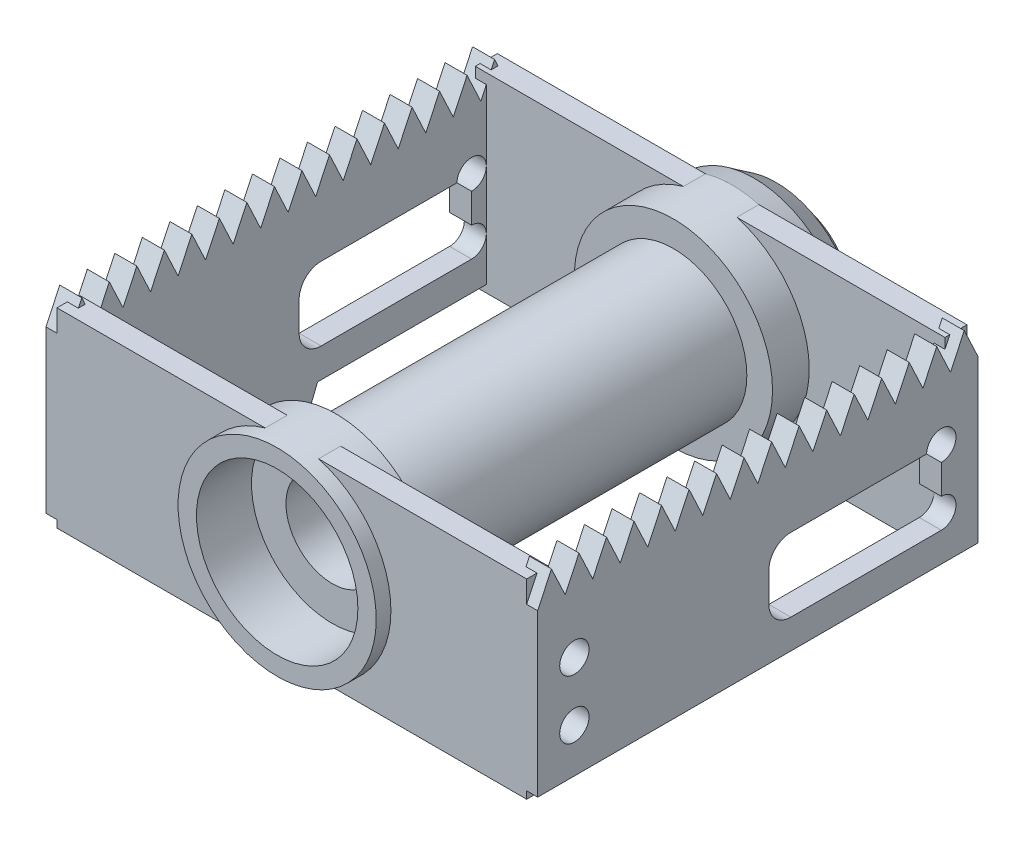
SolidWorks part; units mm, degrees
material "6061-T6 (SS)"
ref_plane "Alzado" through (0, 0, 0) normal (0, 0, 1) x (1, 0, 0)
ref_plane "Planta" through (0, 0, 0) normal (0, 1, 0) x (1, 0, 0)
ref_plane "Vista lateral" through (0, 0, 0) normal (1, 0, 0) x (0, 0, -1)
sketch "Sk_Eje_cuerpo" plane through (0, 0, 0) normal (0, 1, 0) x (1, 0, 0)
  line L0 (-183.5, 84) -> (-186, 84)
  line L1 (-186, 84) -> (-186, 92)
  line L2 (-186, 92) -> (-182.5, 92)
  line L3 (-182.5, 92) -> (-182.5, 138)
  line L4 (-182.5, 138) -> (-186, 138)
  line L5 (-186, 138) -> (-186, 146)
  line L6 (-186, 146) -> (-185.3, 149)
  line L7 (-185.3, 149) -> (-183.3, 152)
  line L8 (-183.3, 152) -> (-180, 154.5)
  line L9 (-180, 154.5) -> (-176.5, 155.7)
  line L10 (-176.5, 155.7) -> (-172.5, 156)
  line L11 (-172.5, 156) -> (-172.5, 147)
  line L12 (-172.5, 147) -> (-183.5, 147)
  line L13 (-183.5, 147) -> (-183.5, 138.5)
  line L14 (-183.5, 138.5) -> (-178.8, 138.5)
  line L15 (-178.8, 138.5) -> (-178.8, 91.5)
  line L16 (-178.8, 91.5) -> (-183.5, 91.5)
  line L17 (-183.5, 91.5) -> (-183.5, 84)
  line L18 (-172.5, 62.1) -> (-172.5, 160) construction
revolve "Eje_cuerpo" add sketch "Sk_Eje_cuerpo" angle 360 about L18
sketch "Sk_Placa_delantera" plane through (0, 0, 0) normal (1, 0, 0) x (0, 0, -1)
  line L0 (86, -12) -> (112, -12)
  line L1 (112, -12) -> (116, -22)
  line L2 (116, -22) -> (120, -12)
  line L3 (120, -12) -> (146, -12)
  line L4 (146, -12) -> (146, 10)
  line L5 (146, 10) -> (144.125, 14)
  line L6 (144.125, 14) -> (142.25, 10)
  line L7 (142.25, 10) -> (140.375, 14)
  line L8 (140.375, 14) -> (138.5, 10)
  line L9 (138.5, 10) -> (136.625, 14)
  line L10 (136.625, 14) -> (134.75, 10)
  line L11 (134.75, 10) -> (132.875, 14)
  line L12 (132.875, 14) -> (131, 10)
  line L13 (131, 10) -> (129.125, 14)
  line L14 (129.125, 14) -> (127.25, 10)
  line L15 (127.25, 10) -> (125.375, 14)
  line L16 (125.375, 14) -> (123.5, 10)
  line L17 (123.5, 10) -> (121.625, 14)
  line L18 (121.625, 14) -> (119.75, 10)
  line L19 (119.75, 10) -> (117.875, 14)
  line L20 (117.875, 14) -> (116, 10)
  line L21 (116, 10) -> (114.125, 14)
  line L22 (114.125, 14) -> (112.25, 10)
  line L23 (112.25, 10) -> (110.375, 14)
  line L24 (110.375, 14) -> (108.5, 10)
  line L25 (108.5, 10) -> (106.625, 14)
  line L26 (106.625, 14) -> (104.75, 10)
  line L27 (104.75, 10) -> (102.875, 14)
  line L28 (102.875, 14) -> (101, 10)
  line L29 (101, 10) -> (99.125, 14)
  line L30 (99.125, 14) -> (97.25, 10)
  line L31 (97.25, 10) -> (95.375, 14)
  line L32 (95.375, 14) -> (93.5, 10)
  line L33 (93.5, 10) -> (91.625, 14)
  line L34 (91.625, 14) -> (89.75, 10)
  line L35 (89.75, 10) -> (87.875, 14)
  line L36 (87.875, 14) -> (86, 10)
  line L37 (86, 10) -> (86, -12)
extrude "Placa_delantera" add sketch "Sk_Placa_delantera" along normal blind 3 from offset 206 offset against normal yes
sketch3d "Sk_Agujero_Placa_delantera_1"
  line L0 (-201.5, -6, -91) -> (-207.5, -6, -91)
  dimension "D1" = 6
sweep "Agujero_Placa_delantera_1" cut path "Sk_Agujero_Placa_delantera_1" circular profile diameter 4 parameters "D3"=4
sketch3d "Sk_Agujero_Placa_delantera_2"
  line L0 (-201.5, 2, -91) -> (-207.5, 2, -91)
  dimension "D1" = 6
sweep "Agujero_Placa_delantera_2" cut path "Sk_Agujero_Placa_delantera_2" circular profile diameter 4 parameters "D3"=4
sketch3d "Sk_Agujero_Placa_delantera_3"
  line L0 (-201.5, -6, -141) -> (-207.5, -6, -141)
  dimension "D1" = 6
sweep "Agujero_Placa_delantera_3" cut path "Sk_Agujero_Placa_delantera_3" circular profile diameter 4 parameters "D3"=4
sketch3d "Sk_Agujero_Placa_delantera_4"
  line L0 (-201.5, 2, -141) -> (-207.5, 2, -141)
  dimension "D1" = 6
sweep "Agujero_Placa_delantera_4" cut path "Sk_Agujero_Placa_delantera_4" circular profile diameter 4 parameters "D3"=4
sketch "Sk_Placa_trasera" plane through (0, 0, 0) normal (1, 0, 0) x (0, 0, -1)
  line L0 (86, -12) -> (146, -12)
  line L1 (146, -12) -> (146, 10)
  line L2 (146, 10) -> (144.125, 14)
  line L3 (144.125, 14) -> (142.25, 10)
  line L4 (142.25, 10) -> (140.375, 14)
  line L5 (140.375, 14) -> (138.5, 10)
  line L6 (138.5, 10) -> (136.625, 14)
  line L7 (136.625, 14) -> (134.75, 10)
  line L8 (134.75, 10) -> (132.875, 14)
  line L9 (132.875, 14) -> (131, 10)
  line L10 (131, 10) -> (129.125, 14)
  line L11 (129.125, 14) -> (127.25, 10)
  line L12 (127.25, 10) -> (125.375, 14)
  line L13 (125.375, 14) -> (123.5, 10)
  line L14 (123.5, 10) -> (121.625, 14)
  line L15 (121.625, 14) -> (119.75, 10)
  line L16 (119.75, 10) -> (117.875, 14)
  line L17 (117.875, 14) -> (116, 10)
  line L18 (116, 10) -> (114.125, 14)
  line L19 (114.125, 14) -> (112.25, 10)
  line L20 (112.25, 10) -> (110.375, 14)
  line L21 (110.375, 14) -> (108.5, 10)
  line L22 (108.5, 10) -> (106.625, 14)
  line L23 (106.625, 14) -> (104.75, 10)
  line L24 (104.75, 10) -> (102.875, 14)
  line L25 (102.875, 14) -> (101, 10)
  line L26 (101, 10) -> (99.125, 14)
  line L27 (99.125, 14) -> (97.25, 10)
  line L28 (97.25, 10) -> (95.375, 14)
  line L29 (95.375, 14) -> (93.5, 10)
  line L30 (93.5, 10) -> (91.625, 14)
  line L31 (91.625, 14) -> (89.75, 10)
  line L32 (89.75, 10) -> (87.875, 14)
  line L33 (87.875, 14) -> (86, 10)
  line L34 (86, 10) -> (86, -12)
extrude "Placa_trasera" add sketch "Sk_Placa_trasera" along normal blind 3 from offset 142 offset against normal yes
sketch3d "Sk_Agujero_Placa_trasera_1"
  line L0 (-137.5, -6, -91) -> (-143.5, -6, -91)
  dimension "D1" = 6
sweep "Agujero_Placa_trasera_1" cut path "Sk_Agujero_Placa_trasera_1" circular profile diameter 4 parameters "D3"=4
sketch3d "Sk_Agujero_Placa_trasera_2"
  line L0 (-137.5, 2, -91) -> (-143.5, 2, -91)
  dimension "D1" = 6
sweep "Agujero_Placa_trasera_2" cut path "Sk_Agujero_Placa_trasera_2" circular profile diameter 4 parameters "D3"=4
sketch3d "Sk_Agujero_Placa_trasera_3"
  line L0 (-137.5, -6, -141) -> (-143.5, -6, -141)
  dimension "D1" = 6
sweep "Agujero_Placa_trasera_3" cut path "Sk_Agujero_Placa_trasera_3" circular profile diameter 4 parameters "D3"=4
sketch3d "Sk_Agujero_Placa_trasera_4"
  line L0 (-137.5, 2, -141) -> (-143.5, 2, -141)
  dimension "D1" = 6
sweep "Agujero_Placa_trasera_4" cut path "Sk_Agujero_Placa_trasera_4" circular profile diameter 4 parameters "D3"=4
sketch "Sk_Marco_interior" plane through (0, 0, 0) normal (0, 0, 1) x (1, 0, 0)
  line L0 (-140.5, -13) -> (-204.5, -13)
  line L1 (-204.5, -13) -> (-204.5, 13)
  line L2 (-204.5, 13) -> (-140.5, 13)
  line L3 (-140.5, 13) -> (-140.5, -13)
  circle A0 centre (-172.5, 0) radius 11
  dimension "DIAM1" = 22
extrude "Marco_interior" add sketch "Sk_Marco_interior" along normal blind 3 from offset 89 offset against normal yes
sketch "Sk_Marco_exterior" plane through (0, 0, 0) normal (0, 0, 1) x (1, 0, 0)
  line L0 (-140.5, -13) -> (-204.5, -13)
  line L1 (-204.5, -13) -> (-204.5, 13)
  line L2 (-204.5, 13) -> (-140.5, 13)
  line L3 (-140.5, 13) -> (-140.5, -13)
  circle A0 centre (-172.5, 0) radius 11
  dimension "DIAM2" = 22
extrude "Marco_exterior" add sketch "Sk_Marco_exterior" along normal blind 3 from offset 146 offset against normal yes
ref_axis "Eje_pedal" through (-172.5, 0, -146) along (0, 0, 1)
sketch "Croquis1" plane through (-139, 0, 0) normal (1, 0, 0) x (0, 0, -1)
  line L0 (117.492, -1) -> (117.492, -5)
  line L1 (120.492, -8) -> (141, -8)
  line L2 (141, -8) -> (141, 2)
  line L3 (141, 2) -> (120.492, 2)
  circle A0 centre (141, -6) radius 2 construction
  arc A1 (117.492, -1) -> (120.492, 2) centre (120.492, -1) cw
  arc A2 (117.492, -5) -> (120.492, -8) centre (120.492, -5) ccw
  dimension "D1" = 3
extrude "Cortar-Extruir2" cut sketch "Croquis1" against normal blind 10
ref_plane "Plano1" through (-173, 0, 0) normal (1, 0, 0) x (0, 0, -1)
mirror "Simetría1" about plane through (-173, 0, 0) normal (1, 0, 0) of "Cortar-Extruir2"
